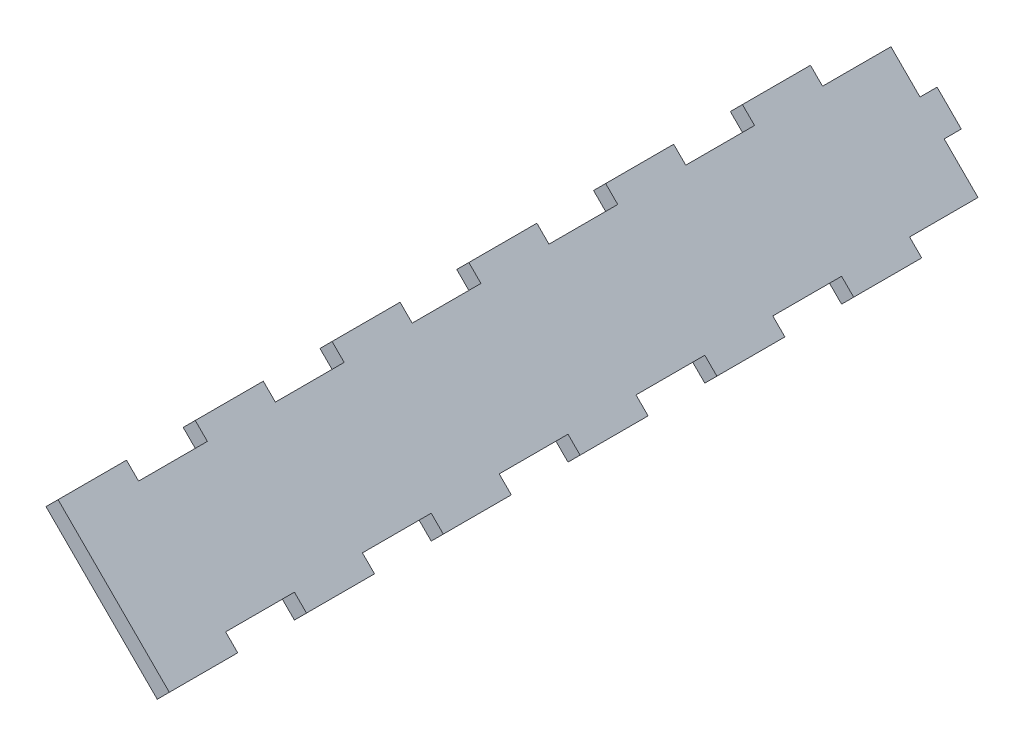
SolidWorks part; units mm, degrees
ref_plane "Front Plane" through (0, 0, 0) normal (0, 0, 1) x (1, 0, 0)
ref_plane "Top Plane" through (0, 0, 0) normal (0, 1, 0) x (1, 0, 0)
ref_plane "Right Plane" through (0, 0, 0) normal (1, 0, 0) x (0, 0, -1)
sketch "Sketch1" plane through (0, 0, 0) normal (0, 0, 1) x (1, 0, 0)
  line L0 (66.9029, 45.85) -> (108.2121, 4.5408)
  line L1 (66.9029, 45.85) -> (71.393, 50.3401)
  line L2 (108.2121, 4.5408) -> (112.7022, 9.0309)
  line L3 (71.393, 50.3401) -> (112.7022, 9.0309)
  line L4 (76.7812, -26.8901) -> (72.2911, -22.4) construction
extrude "Boss-Extrude1" add sketch "Sketch1" along normal up to surface (304.8 mm away)
sketch "Sketch2" plane through (60.8666, 60.8666, 0) normal (0.7071, 0.7071, 0) x (0, 0, -1)
  line L0 (-304.8, -14.8867) -> (0, -14.8867) construction
  line L1 (-279.4, -21.2367) -> (-253.8574, -21.2367)
  line L2 (-279.4, -21.2367) -> (-279.4, -14.8867)
  line L3 (-279.4, -14.8867) -> (-253.8574, -14.8867)
  line L4 (-253.8574, -21.2367) -> (-253.8574, -14.8867)
  line L5 (-304.8, -73.3067) -> (0, -73.3067) construction
  line L6 (-279.4, -66.9567) -> (-253.8574, -66.9567)
  line L7 (-279.4, -66.9567) -> (-279.4, -73.3067)
  line L8 (-279.4, -73.3067) -> (-253.8574, -73.3067)
  line L9 (-253.8574, -66.9567) -> (-253.8574, -73.3067)
extrude "Cut-Extrude1" cut sketch "Sketch2" against normal blind 6.35
pattern_linear "LPattern1" count 6 spacing 50.8 along (0, 0, -1) of "Cut-Extrude1"
sketch "Sketch3" plane through (0, 0, 0) normal (0, 0, -1) x (-1, 0, 0)
  line L0 (-82.1811, 30.5718) -> (-91.1613, 21.5915)
  line L1 (-71.393, 41.3598) -> (-103.722, 9.0309) construction
  line L2 (-91.1613, 21.5915) -> (-95.6515, 26.0817)
  line L3 (-108.2121, 13.521) -> (-75.8832, 45.85) construction
  line L4 (-95.6515, 26.0817) -> (-86.6712, 35.0619)
  line L5 (-86.6712, 35.0619) -> (-82.1811, 30.5718)
  dimension "D1" = 21.6066
  dimension "D2" = 12.7
extrude "Boss-Extrude2" add sketch "Sketch3" along normal blind 6.35
